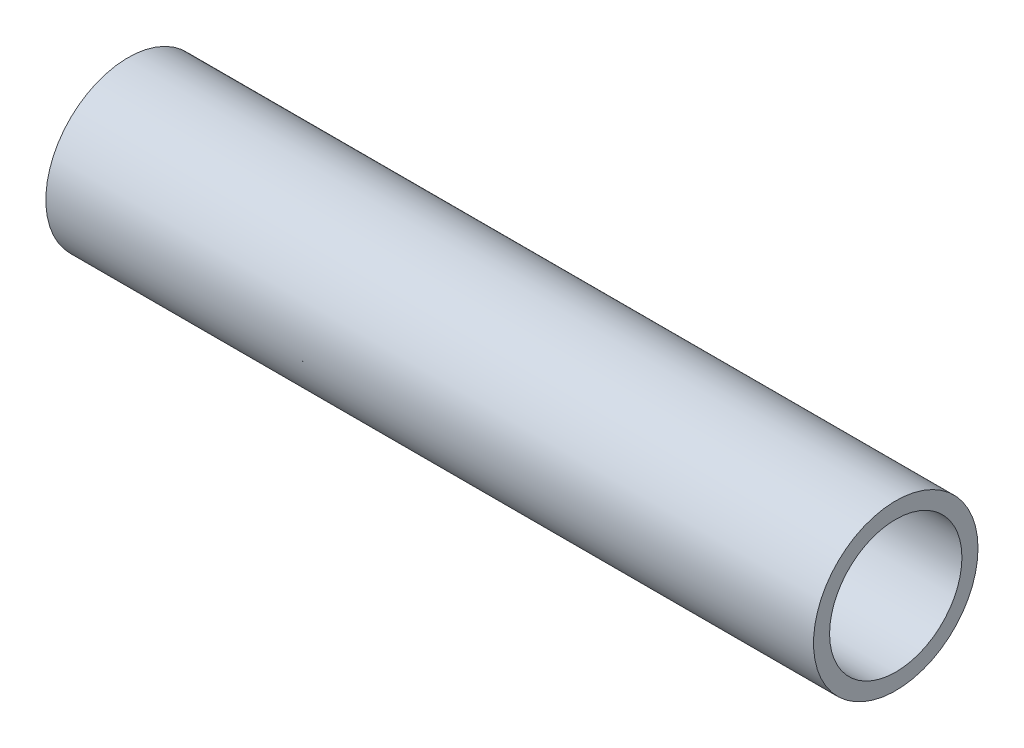
SolidWorks part; units mm, degrees
material "7075-T6 (SN)"
ref_plane "Front Plane" through (0, 0, 0) normal (0, 0, 1) x (1, 0, 0)
ref_plane "Top Plane" through (0, 0, 0) normal (0, 1, 0) x (1, 0, 0)
ref_plane "Right Plane" through (0, 0, 0) normal (1, 0, 0) x (0, 0, -1)
sketch "Sketch1" plane through (0, 0, 0) normal (1, 0, 0) x (0, 0, -1)
  circle A0 centre (0, 0) radius 45.974
  circle A1 centre (0, 0) radius 57.15
  dimension "D1" = 91.948
  dimension "D2" = 114.3
extrude "Boss-Extrude1" add sketch "Sketch1" along normal blind 533.4
sketch "Sketch2" plane through (0, 0, 0) normal (-1, 0, 0) x (0, 0, 1)
  circle A0 centre (0, 0) radius 44.577
  circle A1 centre (0, 0) radius 57.15
  dimension "D1" = 89.154
extrude "Boss-Extrude2" add sketch "Sketch2" against normal blind 95.25
